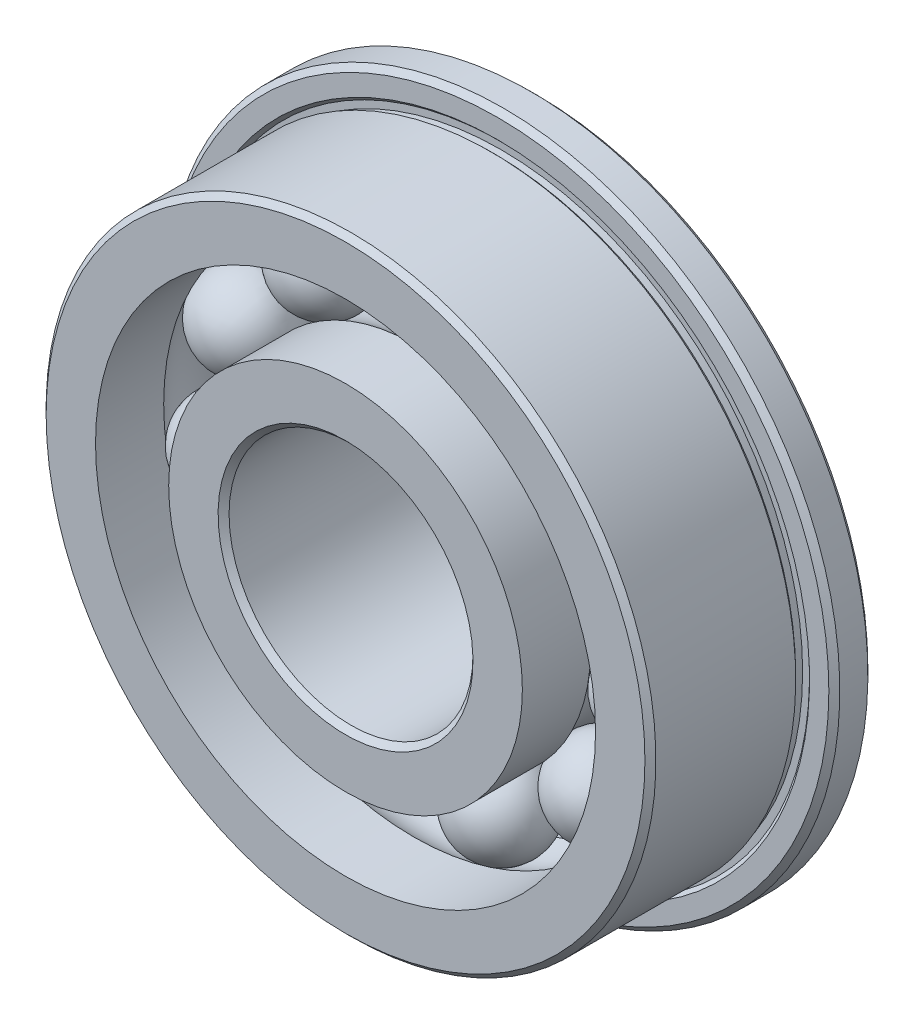
SolidWorks part; units mm, degrees
ref_plane "Front Plane" through (0, 0, 0) normal (0, 0, 1) x (1, 0, 0)
ref_plane "Top Plane" through (0, 0, 0) normal (0, 1, 0) x (1, 0, 0)
ref_plane "Right Plane" through (0, 0, 0) normal (1, 0, 0) x (0, 0, -1)
sketch "Sketch1" plane through (0, 0, 0) normal (1, 0, 0) x (0, 0, -1)
  line L0 (0, 7.9375) -> (0, -7.9375) construction
  line L1 (-2.4892, 7.9375) -> (2.4892, 7.9375) construction
  line L2 (0, 0) -> (2.4892, 0) construction
  line L3 (2.4892, 8.763) -> (2.4892, -8.763) construction
  line L4 (2.4892, -8.763) -> (1.4732, -8.763) construction
  line L5 (2.4892, 3.175) -> (0, 3.175) construction
  line L6 (2.4892, 3.175) -> (2.4892, -3.175) construction
  dimension "OD" = 15.875
  dimension "Width" = 4.9784
  dimension "Flange Dia." = 17.526
  dimension "Flange Thickness" = 1.016
  dimension "ID" = 6.35
sketch "Sketch2" plane through (0, 0, 0) normal (1, 0, 0) x (0, 0, -1)
  line L0 (2.4892, 8.763) -> (1.4732, 8.763)
  line L1 (1.4732, 8.763) -> (1.4732, 8.1171)
  line L2 (1.2936, 7.9375) -> (-2.4892, 7.9375)
  line L3 (-2.4892, 7.9375) -> (-2.4892, 6.5088)
  line L4 (-2.4892, 6.5088) -> (-0.7144, 6.5088)
  line L5 (2.4892, 8.763) -> (2.4892, -8.763) construction
  line L6 (2.4892, 6.5088) -> (2.4892, 8.763)
  line L7 (2.4892, 3.175) -> (-2.4892, 3.175)
  line L8 (-2.4892, 3.175) -> (-2.4892, 4.6037)
  line L9 (-2.4892, 4.6037) -> (-0.7144, 4.6037)
  line L10 (2.4892, 4.6037) -> (2.4892, 3.175)
  line L11 (0, 7.9375) -> (0, 3.175) construction
  line L12 (-1.1906, 5.5562) -> (1.1906, 5.5562) construction
  line L13 (0.7144, 6.5088) -> (2.4892, 6.5088)
  line L14 (0.7144, 4.6037) -> (2.4892, 4.6037)
  line L15 (1.4732, 8.1171) -> (1.563, 8.0273)
  line L16 (1.563, 8.0273) -> (1.563, 7.8477)
  line L17 (1.563, 7.8477) -> (1.3834, 7.8477)
  line L18 (1.3834, 7.8477) -> (1.2936, 7.9375)
  line L19 (1.4732, 7.9375) -> (1.563, 7.8477) construction
  line L20 (1.563, 8.0273) -> (1.3834, 7.8477) construction
  line L21 (1.2936, 7.9375) -> (1.4732, 7.9375) construction
  line L22 (1.4732, 7.9375) -> (1.4732, 8.1171) construction
  circle A0 centre (0, 5.5563) radius 1.1906 construction
  arc A1 (-0.7144, 6.5088) -> (0.7144, 6.5088) centre (0, 5.5563) cw
  arc A2 (-0.7144, 4.6037) -> (0.7144, 4.6037) centre (0, 5.5563) ccw
  dimension "D1" = 4.7625
  dimension "Ball Dia." = 2.3813
  dimension "D2" = 135
  dimension "D3" = 0.254
  dimension "D4" = 1.905
  dimension "Race Thickness" = 1.4288
revolve "Revolve1" add sketch "Sketch2" angle 360 about L2
fillet "Fillet1" radius 0.1429 3 edges at (0, -8.763, -2.4892) (0, -8.763, -1.4732) (0, -7.9375, 2.4892) profile chamfer
sketch "Sketch3" plane through (0, 0, 0) normal (0, 0, 1) x (1, 0, 0)
  line L0 (-3.175, 0) -> (3.175, 0) construction
  line L1 (-7.9375, 0) -> (7.9375, 0) construction
  point P5 (0, 0)
  dimension "ID2" = 6.35
  dimension "OD2" = 15.875
fillet "Fillet2" radius 0.1429 2 edges at (0, -3.175, -2.4892) (0, -3.175, 2.4892) profile chamfer
sketch "Sketch7" plane through (0, 0, 0) normal (0, 0, 1) x (1, 0, 0)
  line L0 (0, 6.7469) -> (0, 4.3656)
  line L1 (0, 8.763) -> (0, -8.763) construction
  line L2 (-1.4801, 6.7469) -> (0, 0) construction
  line L3 (0, 0) -> (1.4801, 6.7469) construction
  line L4 (1.4801, 6.7469) -> (-1.4801, 6.7469) construction
  circle A0 centre (0, 5.5563) radius 1.1906 construction
  circle A1 centre (0, 0) radius 6.7469 construction
  circle A2 centre (0, 0) radius 4.3656 construction
  arc A4 (0, 6.7469) -> (0, 4.3656) centre (0, 5.5563) ccw
  dimension "D1" = 24.747
revolve "Revolve3" add sketch "Sketch7" angle 360 about L0
pattern_circular "CirPattern3" count 11 over 360 about axis through (0, 0, 0) along (0, 0, -1) of bodies 107
sketch "Sketch8" [suppressed] plane through (0, 0, 0) normal (1, 0, 0) x (0, 0, -1)
  line L1 (-1.1906, 2.0241) -> (-1.0477, 2.0241)
  line L2 (-1.1906, 2.0241) -> (-1.1906, 2.1431)
  line L3 (-1.1906, 2.1431) -> (-1.0477, 2.1431)
  line L4 (-1.0477, 2.0241) -> (-1.0477, 2.1431)
  line L5 (1.1906, 2.0241) -> (1.0478, 2.0241)
  line L6 (1.1906, 2.0241) -> (1.1906, 2.1431)
  line L7 (1.1906, 2.1431) -> (1.0478, 2.1431)
  line L8 (1.0478, 2.0241) -> (1.0478, 2.1431)
  line L9 (1.1906, 1.5478) -> (1.0478, 1.5478)
  line L10 (1.1906, 1.5478) -> (1.1906, 1.4287)
  line L11 (1.1906, 1.4287) -> (1.0478, 1.4287)
  line L12 (1.0478, 1.5478) -> (1.0478, 1.4287)
  line L13 (-1.1906, 1.5478) -> (-1.0477, 1.5478)
  line L14 (-1.1906, 1.5478) -> (-1.1906, 1.4287)
  line L15 (-1.1906, 1.4287) -> (-1.0477, 1.4287)
  line L16 (-1.0477, 1.5478) -> (-1.0477, 1.4287)
  dimension "D1" = 0.4762
  dimension "D2" = 0.5715
revolve "Cut-Revolve1" [suppressed] cut sketch "Sketch8" angle 360 about L2
sketch "Sketch9" [suppressed] plane through (0, 0, 0) normal (1, 0, 0) x (0, 0, -1)
  line L0 (-1.0477, 2.1431) -> (-1.0477, 1.8657)
  line L1 (-1.0477, 1.8657) -> (-1.1192, 1.7419)
  line L2 (-1.1192, 1.7419) -> (-1.1192, 1.4645)
  line L3 (1.1192, 1.4645) -> (1.1192, 1.4287) construction
  line L4 (1.0478, 2.1431) -> (1.0478, 1.8657)
  line L5 (1.0478, 1.8657) -> (1.1192, 1.7419)
  line L6 (1.1192, 1.7419) -> (1.1192, 1.4645)
  line L7 (1.1906, 1.4287) -> (1.0478, 1.4287) construction
  line L8 (-1.0835, 2.1431) -> (-1.0835, 1.8752)
  line L9 (-1.0835, 1.8752) -> (-1.1549, 1.7515)
  line L10 (-1.1549, 1.7515) -> (-1.1549, 1.4645)
  line L11 (-1.0477, 2.1431) -> (-1.0835, 2.1431)
  line L12 (-1.1192, 1.4645) -> (-1.1549, 1.4645)
  line L13 (1.0835, 2.1431) -> (1.0835, 1.8752)
  line L14 (1.0835, 1.8752) -> (1.1549, 1.7515)
  line L15 (1.1549, 1.7515) -> (1.1549, 1.4645)
  line L16 (1.0478, 2.1431) -> (1.0835, 2.1431)
  line L17 (1.1192, 1.4645) -> (1.1549, 1.4645)
  line L18 (-1.0477, 1.8657) -> (-1.0477, 2.6) construction
  line L19 (1.0478, 1.8657) -> (1.0478, 2.1431) construction
  line L20 (-1.0477, 1.4287) -> (-1.1906, 1.4287) construction
  line L22 (-1.1192, 1.4645) -> (-1.1192, 1.4287) construction
  dimension "D2" = 150
  dimension "D1" = 150
  dimension "D5" = 0.1429
  dimension "D3" = 0.0357
  dimension "D4" = 0.0357
revolve "Revolve4" [suppressed] add sketch "Sketch9" angle 360 about L2
ref_axis "Center Axis 1" through (0, 0, -0.8731) along (0, 0, 1)
ref_plane "Contact Plane 1" through (0, 0, -1.4732) normal (0, 0, 1) x (1, 0, 0)
equation "\"Ball Dia.@Sketch2\"=\"D1@Sketch2\"*.5"
equation "\"D3@Sketch2\"=\"Flange Thickness@Sketch1\"/4"
equation "\"D1@Fillet1\"=\"Race Thickness@Sketch2\"/10"
equation "\"ID2@Sketch3\" = \"ID@Sketch1\""
equation "\"OD2@Sketch3\" = \"OD@Sketch1\""
equation "\"D1@Fillet2\"=\"Race Thickness@Sketch2\"/10"
equation "\"D1@CirPattern3\"=360/\"D1@Sketch7\"-4"
equation "\"D1@Sketch8\"=\"Race Thickness@Sketch2\"/3"
equation "\"D2@Sketch8\"=\"Race Thickness@Sketch2\"/2.5"
equation "\"D3@Sketch9\"=\"D5@Sketch9\"/4"
equation "\"D4@Sketch9\"=\"D5@Sketch9\"/4"
equation "\"D1@Sketch9\"=\"D2@Sketch9\""
equation "\"D4@Sketch2\"=\"D1@Sketch2\"*.4"
